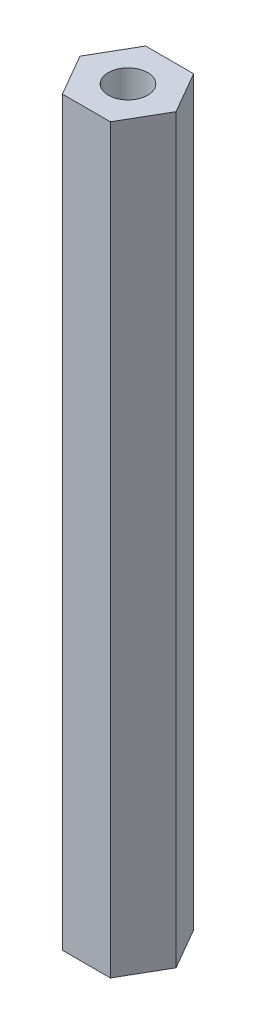
SolidWorks part; units mm, degrees
material "Nylon 101"
ref_plane "Plan de face" through (0, 0, 0) normal (0, 0, 1) x (1, 0, 0)
ref_plane "Plan de dessus" through (0, 0, 0) normal (0, 1, 0) x (1, 0, 0)
ref_plane "Plan de droite" through (0, 0, 0) normal (1, 0, 0) x (0, 0, -1)
sketch "Esquisse1" plane through (0, 0, 0) normal (0, 1, 0) x (1, 0, 0)
  line L1 (3.1754, 0) -> (1.5877, 2.75)
  line L2 (1.5877, 2.75) -> (-1.5877, 2.75)
  line L3 (-1.5877, 2.75) -> (-3.1754, 0)
  line L4 (-3.1754, 0) -> (-1.5877, -2.75)
  line L5 (-1.5877, -2.75) -> (1.5877, -2.75)
  line L6 (1.5877, -2.75) -> (3.1754, 0)
  circle A0 centre (0, 0) radius 2.75 construction
  dimension "D1" = 5.5
extrude "Boss.-Extru.1" add sketch "Esquisse1" along normal blind 24.5 and the other way blind 24.5
hole_wizard "Dégagement M31" positions "Esquisse2" profile "Esquisse3" hole size "M3" standard "Ansi Metric"
sketch "Esquisse2" plane through (0, 24.5, 0) normal (0, 1, 0) x (1, 0, 0)
  point P0 (0, 0)
sketch "Esquisse3" plane through (0, 24.5, 0) normal (1, 0, 0) x (0, 0, 1)
  line L0 (0, 0) -> (0, 7.1311)
  line L1 (0, 7.1311) -> (1.3, 6.35)
  line L2 (1.3, 6.35) -> (1.3, 0)
  line L5 (1.3, 0) -> (0, 0)
  line L10 (0, 7.1311) -> (-1.3, 6.35) construction
  line L11 (0, -6.35) -> (0, 107.95) construction
  dimension "Diamètre du perçage" = 2.6
  dimension "Profondeur du perçage" = 6.35
  dimension "Angle de pointe" = 118
mirror "Symétrie1" about plane through (0, 0, 0) normal (0, 1, 0) of "Dégagement M31"
